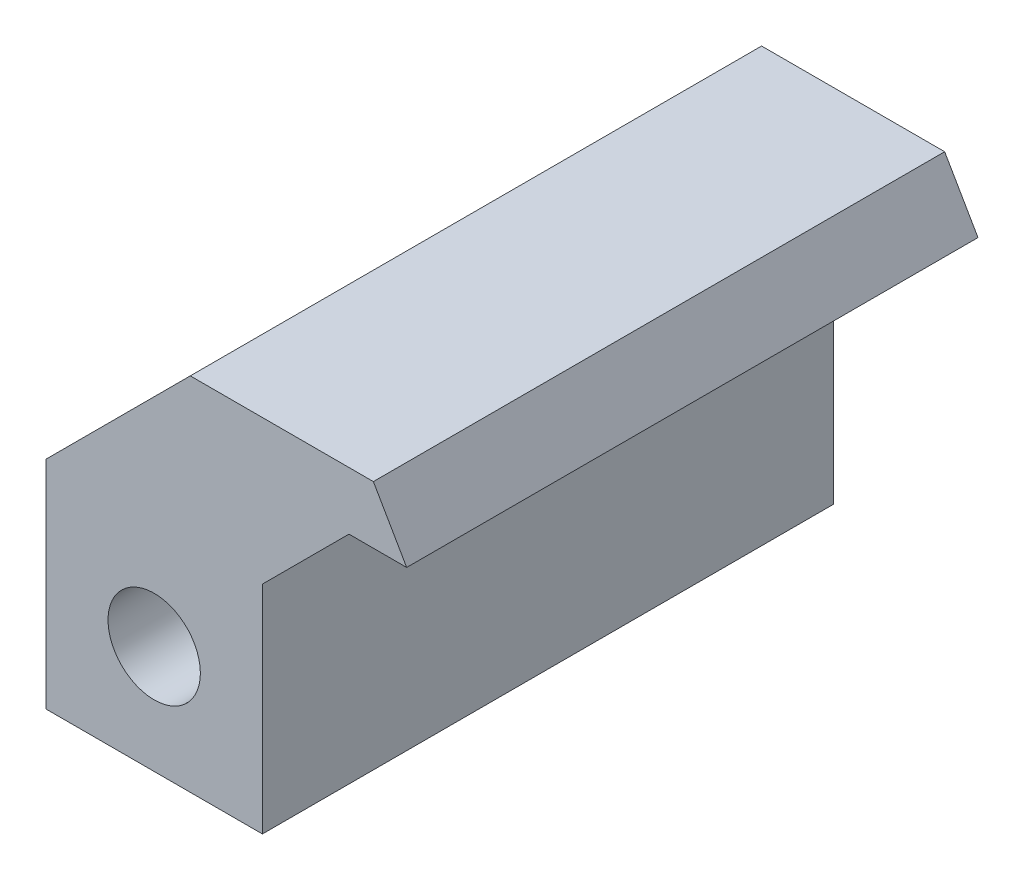
SolidWorks part; units mm, degrees
ref_plane "Front Plane" through (0, 0, 0) normal (0, 0, 1) x (1, 0, 0)
ref_plane "Top Plane" through (0, 0, 0) normal (0, 1, 0) x (1, 0, 0)
ref_plane "Right Plane" through (0, 0, 0) normal (1, 0, 0) x (0, 0, -1)
sketch "Sketch1" plane through (0, 0, 0) normal (0, 0, 1) x (1, 0, 0)
  line L1 (-3.75, -3.75) -> (3.75, -3.75)
  line L2 (-3.75, -3.75) -> (-3.75, 3.75)
  line L3 (-3.75, 3.75) -> (3.75, 3.75)
  line L4 (3.75, -3.75) -> (3.75, 3.75)
  line L5 (-3.75, -3.75) -> (3.75, 3.75) construction
  line L6 (-3.75, 3.75) -> (3.75, -3.75) construction
  circle A0 centre (0, 0) radius 1.6
  point P0 (0, 0)
  dimension "D3" = 3.2
  dimension "D1" = 7.5
  dimension "D2" = 7.5
extrude "Boss-Extrude1" add sketch "Sketch1" along normal blind 9.9 and the other way blind 9.9
sketch "Sketch2" plane through (0, 0, 9.9) normal (0, 0, 1) x (1, 0, 0)
  line L0 (3.75, 3.75) -> (6.75, 6.75)
  line L1 (6.75, 6.75) -> (8.75, 6.75)
  line L2 (8.75, 6.75) -> (7.5953, 8.75)
  line L3 (7.5953, 8.75) -> (1.25, 8.75)
  line L4 (1.25, 8.75) -> (-3.75, 3.75)
  line L6 (3.75, 3.75) -> (-3.75, 3.75) construction
  line L7 (3.75, 3.75) -> (-3.75, 3.75)
  dimension "D1" = 60
  dimension "D2" = 2
  dimension "D3" = 3
  dimension "D4" = 45
  dimension "D5" = 2
extrude "Boss-Extrude2" add sketch "Sketch2" against normal up to surface (19.8 mm away) contours L4 L7 L0 L1 L2 L3 up to face at (1.6, 0, -9.9)
